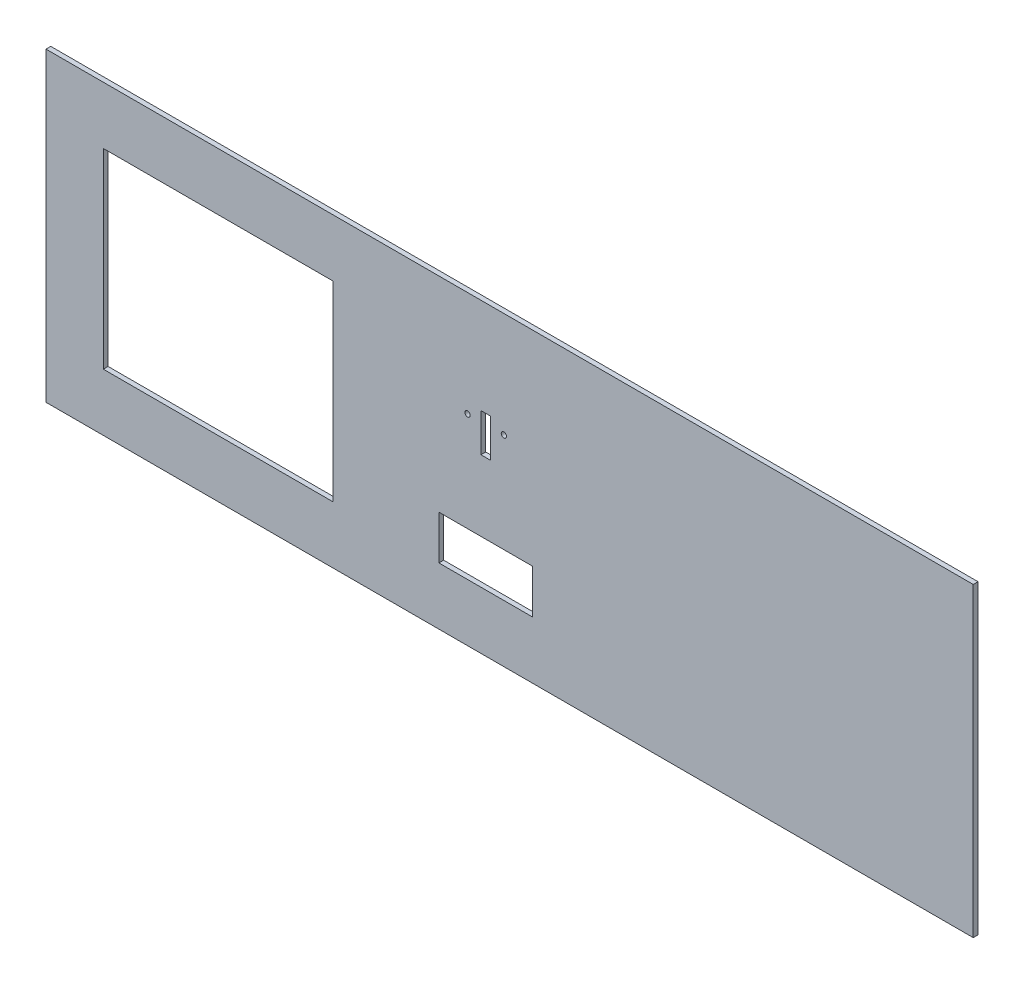
SolidWorks part; units mm, degrees
ref_plane "Front Plane" through (0, 0, 0) normal (0, 0, 1) x (1, 0, 0)
ref_plane "Top Plane" through (0, 0, 0) normal (0, 1, 0) x (1, 0, 0)
ref_plane "Right Plane" through (0, 0, 0) normal (1, 0, 0) x (0, 0, -1)
sketch "Sketch1" plane through (0, 0, 0) normal (0, 0, 1) x (1, 0, 0)
  line L1 (-307.975, -101.6) -> (307.975, -101.6)
  line L2 (-307.975, -101.6) -> (-307.975, 101.6)
  line L3 (-307.975, 101.6) -> (307.975, 101.6)
  line L4 (307.975, -101.6) -> (307.975, 101.6)
  line L5 (-307.975, -101.6) -> (307.975, 101.6) construction
  line L6 (-307.975, 101.6) -> (307.975, -101.6) construction
  point P0 (0, 0)
  dimension "D1" = 203.2
  dimension "D2" = 615.95
extrude "Boss-Extrude1" add sketch "Sketch1" along normal blind 3.175
sketch "Sketch2" plane through (0, 0, 3.175) normal (0, 0, 1) x (1, 0, 0)
  line L0 (307.975, 101.6) -> (-307.975, 101.6) construction
  line L1 (-269.875, -63.5) -> (-117.475, -63.5)
  line L2 (-269.875, -63.5) -> (-269.875, 63.5)
  line L3 (-269.875, 63.5) -> (-117.475, 63.5)
  line L4 (-117.475, -63.5) -> (-117.475, 63.5)
  line L5 (-307.975, 101.6) -> (-307.975, -101.6) construction
  dimension "D1" = 38.1
  dimension "D2" = 38.1
  dimension "D3" = 127
  dimension "D4" = 152.4
extrude "Cut-Extrude1" cut sketch "Sketch2" against normal through all
sketch "Sketch3" plane through (0, 0, 3.175) normal (0, 0, 1) x (1, 0, 0)
  line L0 (-117.475, -63.5) -> (-117.475, 63.5) construction
  line L1 (-19.05, 12.7) -> (-12.7, 12.7)
  line L2 (-19.05, 12.7) -> (-19.05, 38.1)
  line L3 (-19.05, 38.1) -> (-12.7, 38.1)
  line L4 (-12.7, 12.7) -> (-12.7, 38.1)
  line L5 (-19.05, 12.7) -> (-12.7, 38.1) construction
  line L6 (-19.05, 38.1) -> (-12.7, 12.7) construction
  point P0 (-15.875, 25.4)
  dimension "D1" = 25.4
  dimension "D2" = 6.35
  dimension "D3" = 101.6
  dimension "D4" = 25.4
extrude "Cut-Extrude2" cut sketch "Sketch3" against normal through all
sketch "Sketch4" plane through (0, 0, 3.175) normal (0, 0, 1) x (1, 0, 0)
  line L0 (-15.875, 38.1) -> (-15.875, 12.7) construction
  line L1 (-12.7, 38.1) -> (-19.05, 38.1) construction
  line L2 (-19.05, 12.7) -> (-12.7, 12.7) construction
  circle A0 centre (-3.81, 31.75) radius 1.75
  circle A1 centre (-27.94, 31.75) radius 1.75
  point P10 (-3.81, 29.8772)
  dimension "D2" = 3.5
  dimension "D1" = 24.13
  dimension "D3" = 6.35
extrude "Cut-Extrude3" cut sketch "Sketch4" against normal through all
sketch "Sketch5" plane through (0, 0, 3.175) normal (0, 0, 1) x (1, 0, 0)
  line L0 (-269.875, -63.5) -> (-117.475, -63.5) construction
  line L1 (-46.99, -63.5) -> (15.24, -63.5)
  line L2 (-46.99, -63.5) -> (-46.99, -34.29)
  line L3 (-46.99, -34.29) -> (15.24, -34.29)
  line L4 (15.24, -63.5) -> (15.24, -34.29)
  line L5 (-46.99, -63.5) -> (15.24, -34.29) construction
  line L6 (-46.99, -34.29) -> (15.24, -63.5) construction
  line L7 (-15.875, 38.1) -> (-15.875, 12.7) construction
  line L8 (-12.7, 38.1) -> (-19.05, 38.1) construction
  line L9 (-19.05, 12.7) -> (-12.7, 12.7) construction
  point P0 (-15.875, -48.895)
  dimension "D1" = 29.21
  dimension "D2" = 62.23
extrude "Cut-Extrude4" cut sketch "Sketch5" against normal through all
